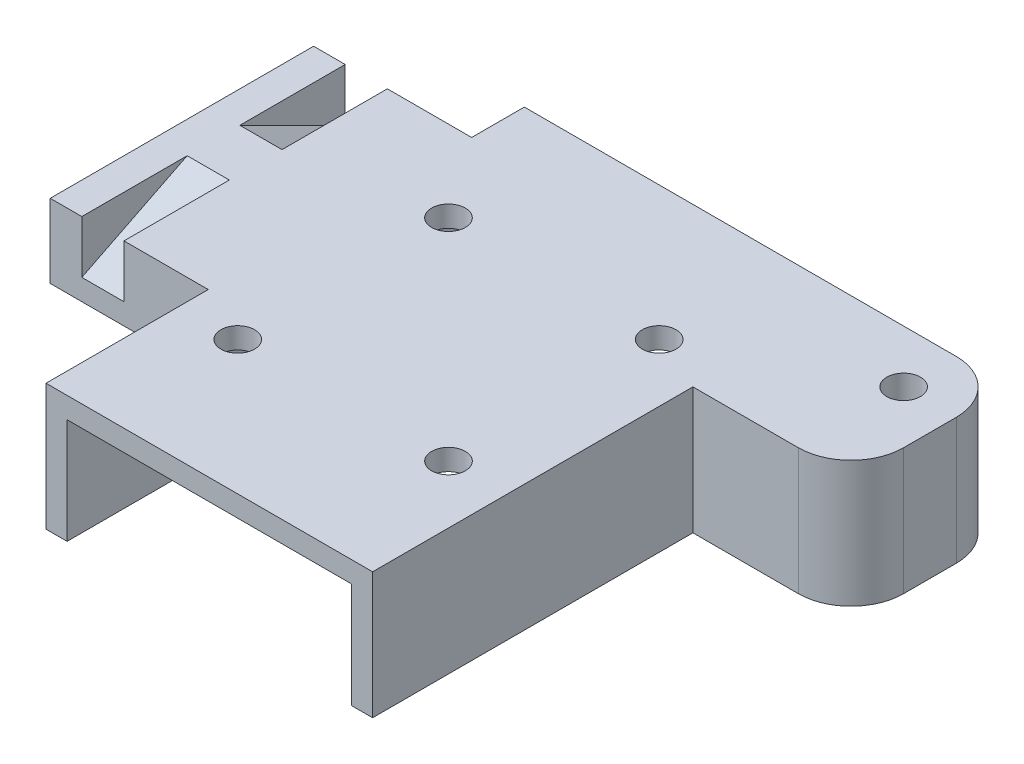
SolidWorks part; units mm, degrees
ref_plane "Front Plane" through (0, 0, 0) normal (0, 0, 1) x (1, 0, 0)
ref_plane "Top Plane" through (0, 0, 0) normal (0, 1, 0) x (1, 0, 0)
ref_plane "Right Plane" through (0, 0, 0) normal (1, 0, 0) x (0, 0, -1)
sketch "Sketch1" plane through (0, 0, 0) normal (0, 1, 0) x (1, 0, 0)
  line L1 (0, 0) -> (31, 0)
  line L2 (0, 0) -> (0, 45.4)
  line L3 (0, 45.4) -> (31, 45.4)
  line L4 (31, 0) -> (31, 45.4)
  dimension "D1" = 31
  dimension "D2" = 45.4
extrude "Boss-Extrude1" add sketch "Sketch1" along normal blind 12
sketch "Sketch2" plane through (0, 0, 0) normal (0, 0, 1) x (1, 0, 0)
  line L0 (0, 0) -> (31, 0) construction
  line L1 (2, 0) -> (29, 0)
  line L2 (2, 0) -> (2, 10)
  line L3 (2, 10) -> (29, 10)
  line L4 (29, 0) -> (29, 10)
  line L5 (0, 12) -> (0, 0) construction
  line L6 (31, 12) -> (31, 0) construction
  dimension "D1" = 2
  dimension "D2" = 2
  dimension "D3" = 10
extrude "Cut-Extrude1" cut sketch "Sketch2" against normal through all
sketch "Sketch3" plane through (0, 12, 0) normal (0, 1, 0) x (1, 0, 0)
  line L0 (15.5, 45.4) -> (15.5, 0) construction
  line L5 (5.5, 12.7) -> (25.5, 12.7) construction
  line L6 (5.5, 12.7) -> (5.5, 32.7) construction
  line L7 (5.5, 32.7) -> (25.5, 32.7) construction
  line L8 (25.5, 12.7) -> (25.5, 32.7) construction
  line L9 (5.5, 12.7) -> (25.5, 32.7) construction
  line L10 (5.5, 32.7) -> (25.5, 12.7) construction
  line L11 (31, 45.4) -> (0, 45.4) construction
  line L12 (0, 0) -> (31, 0) construction
  line L13 (0, 22.7) -> (31, 22.7) construction
  line L14 (0, 45.4) -> (0, 0) construction
  line L15 (31, 0) -> (31, 45.4) construction
  circle A0 centre (5.5, 32.7) radius 1.6
  circle A1 centre (25.5, 32.7) radius 1.6
  circle A2 centre (25.5, 12.7) radius 1.6
  circle A3 centre (5.5, 12.7) radius 1.6
  point P0 (15.5, 22.7)
  dimension "D3" = 3.2
  dimension "D1" = 20
  dimension "D2" = 20
extrude "Cut-Extrude2" cut sketch "Sketch3" against normal blind 10
sketch "Sketch4" plane through (0, 0, 0) normal (-1, 0, 0) x (0, 0, 1)
  line L0 (-45.4, 12) -> (0, 12) construction
  line L1 (-15, 12) -> (0, 12)
  line L2 (-15, 12) -> (-15, 0)
  line L3 (-15, 0) -> (0, 0)
  line L4 (0, 12) -> (0, 0)
  dimension "D1" = 15
extrude "Boss-Extrude2" add sketch "Sketch4" along normal blind 15
sketch "Sketch5" plane through (0, 12, 0) normal (0, 1, 0) x (1, 0, 0)
  line L2 (-15, 0) -> (31, 0) construction
  line L3 (0, 45.4) -> (0, 15) construction
  circle A0 centre (-10, 5) radius 1.6
  dimension "D1" = 3.2
  dimension "D2" = 5
  dimension "D3" = 10
extrude "Cut-Extrude3" cut sketch "Sketch5" against normal blind 20
fillet "Fillet1" radius 5 2 edges at (-15, 6, -15) (-15, 6, 0)
sketch "Sketch6" plane through (31, 0, 0) normal (1, 0, 0) x (0, 0, -1)
  line L9 (5, 0) -> (10, 0)
  line L10 (0, 0) -> (45.4, 0) construction
  line L11 (10, 0) -> (10, 4.7)
  line L12 (10, 4.7) -> (25, 4.7)
  line L13 (25, 4.7) -> (25, 0)
  line L14 (25, 0) -> (30, 0)
  line L15 (30, 0) -> (30, 12)
  line L16 (30, 12) -> (5, 12)
  line L17 (5, 12) -> (5, 0)
  line L18 (0, 12) -> (45.4, 12) construction
  line L19 (0, 12) -> (0, 0) construction
  dimension "D1" = 5
  dimension "D2" = 5
  dimension "D3" = 4.7
  dimension "D4" = 15
  dimension "D5" = 5
extrude "Boss-Extrude3" add sketch "Sketch6" along normal blind 15
chamfer "Chamfer1" distance 5 angle 45 2 edges at (38.5, 0, -5) (38.5, 0, -30)
ref_plane "Plane1" through (43, 0, 0) normal (1, 0, 0) x (0, 0, -1)
sketch "Sketch7" plane through (43, 0, 0) normal (1, 0, 0) x (0, 0, -1)
  line L0 (5, 7) -> (15, 12)
  line L1 (5, 12) -> (5, 5) construction
  line L3 (15, 12) -> (5, 12)
  line L4 (5, 12) -> (5, 7)
  line L5 (30, 7) -> (20, 12)
  line L6 (30, 5) -> (30, 12) construction
  line L7 (20, 12) -> (30, 12)
  line L8 (30, 12) -> (30, 7)
  line L9 (30, 12) -> (5, 12) construction
  dimension "D1" = 5
  dimension "D2" = 5
  dimension "D3" = 10
  dimension "D4" = 10
extrude "Cut-Extrude4" cut sketch "Sketch7" against normal blind 4
mirror "Mirror1" [suppressed] of bodies 111 105
delete or keep bodies "Body-Delete/Keep 1" [suppressed] type delete bodies bodies 111
mirror "Mirror2" about plane through (31, 12, 0) normal (-1, 0, 0) of bodies 111 105
mirror "Mirror3" about plane through (62, 12, -45.4) normal (0, 0, 1) of bodies 107
delete or keep bodies "Body-Delete/Keep 2" type delete bodies bodies 111 107
mirror "Mirror4" [suppressed] of bodies 111 105
delete or keep bodies "Body-Delete/Keep 3" [suppressed] type delete bodies bodies 111
sketch "Sketch10" [suppressed] plane through (46, 0, 0) normal (1, 0, 0) x (0, 0, -1)
  line L0 (60.8, 12) -> (85.8, 12) construction
  line L1 (80.8, 12) -> (85.8, 12)
  line L2 (80.8, 12) -> (80.8, -14.5)
  line L3 (80.8, -14.5) -> (85.8, -14.5)
  line L4 (85.8, 12) -> (85.8, -14.5)
  line L5 (80.8, 0) -> (80.8, 4.7) construction
  line L6 (85.8, 12) -> (85.8, 5) construction
  dimension "D1" = 26.5
extrude "Boss-Extrude7" [suppressed] add sketch "Sketch10" along normal blind 2
sketch "Sketch11" [suppressed] plane through (46, 0, 0) normal (-1, 0, 0) x (0, 0, 1)
  line L0 (-80.8, 0) -> (-80.8, -14.5) construction
  line L1 (-85.8, -14.5) -> (-80.8, -14.5)
  line L2 (-85.8, -14.5) -> (-85.8, -13)
  line L3 (-85.8, -13) -> (-80.8, -13)
  line L4 (-80.8, -14.5) -> (-80.8, -13)
  dimension "D1" = 1.5
extrude "Boss-Extrude8" [suppressed] add sketch "Sketch11" along normal blind 10
fillet "Fillet2" [suppressed] radius 7.5
